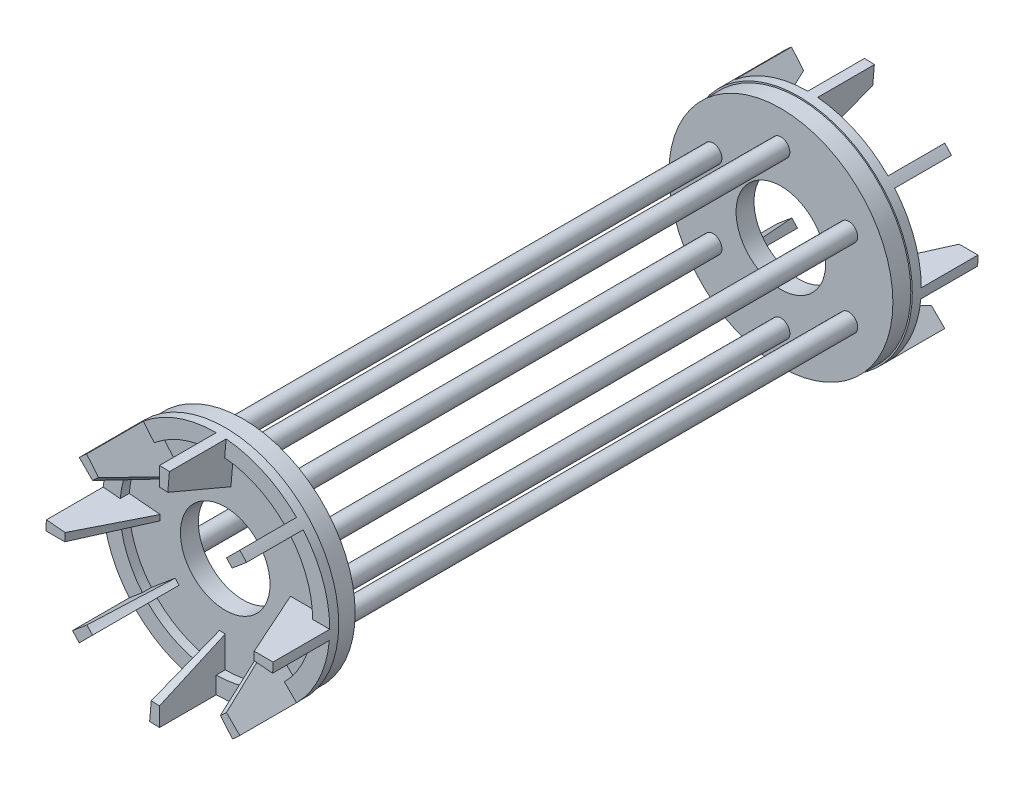
SolidWorks part; units mm, degrees
ref_plane "Front Plane" through (0, 0, 0) normal (0, 0, 1) x (1, 0, 0)
ref_plane "Top Plane" through (0, 0, 0) normal (0, 1, 0) x (1, 0, 0)
ref_plane "Right Plane" through (0, 0, 0) normal (1, 0, 0) x (0, 0, -1)
sketch "Sketch1" plane through (0, 0, 0) normal (0, 0, 1) x (1, 0, 0)
  circle A0 centre (0, 0) radius 5
  circle A1 centre (0, 0) radius 12.5
  dimension "D1" = 10
  dimension "D2" = 25
extrude "Boss-Extrude1" add sketch "Sketch1" along normal blind 2
ref_plane "Plane1" through (0, 0, -30) normal (0, 0, 1) x (1, 0, 0)
sketch "Sketch3" plane through (0, 0, 2) normal (0, 0, 1) x (1, 0, 0)
  circle A0 centre (0, 0) radius 12.6659
  circle A1 centre (0, 0) radius 10.7541
extrude "Boss-Extrude4" add sketch "Sketch3" along normal blind 1
sketch "Sketch4" plane through (0, 0, 0) normal (1, 0, 0) x (0, 0, -1)
  line L2 (-9.3301, 12.6659) -> (-9.3301, 10.5659)
  line L3 (-9.3301, 10.5659) -> (-2, 7.2853)
  line L4 (-2, 12.6659) -> (-2, 7.2853)
  line L5 (-9.3125, 0) -> (2.5739, 0) construction
  line L6 (-2, 12.6659) -> (-9.3301, 12.6659)
  line L8 (-2, 12.6659) -> (-3, 12.6659) construction
revolve "Revolve1" add sketch "Sketch4" angle 5 about L5
pattern_circular "CirPattern1" count 8 over 360 about axis through (0, 0, 9.3125) along (0, 0, -1) of "Revolve1"
sketch "Sketch5" plane through (0, 0, 0) normal (0, 0, -1) x (-1, 0, 0)
  line L0 (0, 5) -> (0, 12.5) construction
  circle A0 centre (0, 8.75) radius 1
  circle A1 centre (0, 0) radius 5 construction
  circle A2 centre (0, 0) radius 12.5 construction
  point P11 (0, 8.75)
  dimension "D1" = 2
extrude "Boss-Extrude5" add sketch "Sketch5" along normal blind 30
pattern_circular "CirPattern2" count 6 over 360 about axis through (0, 0, 9.3125) along (0, 0, -1) of "Boss-Extrude5"
mirror "Mirror4" about plane through (0, 0, -30) normal (0, 0, 1) of bodies 110
sketch "Sketch6" plane through (0, 0, 0) normal (1, 0, 0) x (0, 0, -1)
  line L0 (0, 0) -> (60, 0) construction
  line L1 (0, -12.5) -> (0, 12.5) construction
  line L2 (60, 12.5) -> (60, -12.5) construction
  circle A0 centre (30, 0) radius 16.6942
  point P9 (0, 0)
